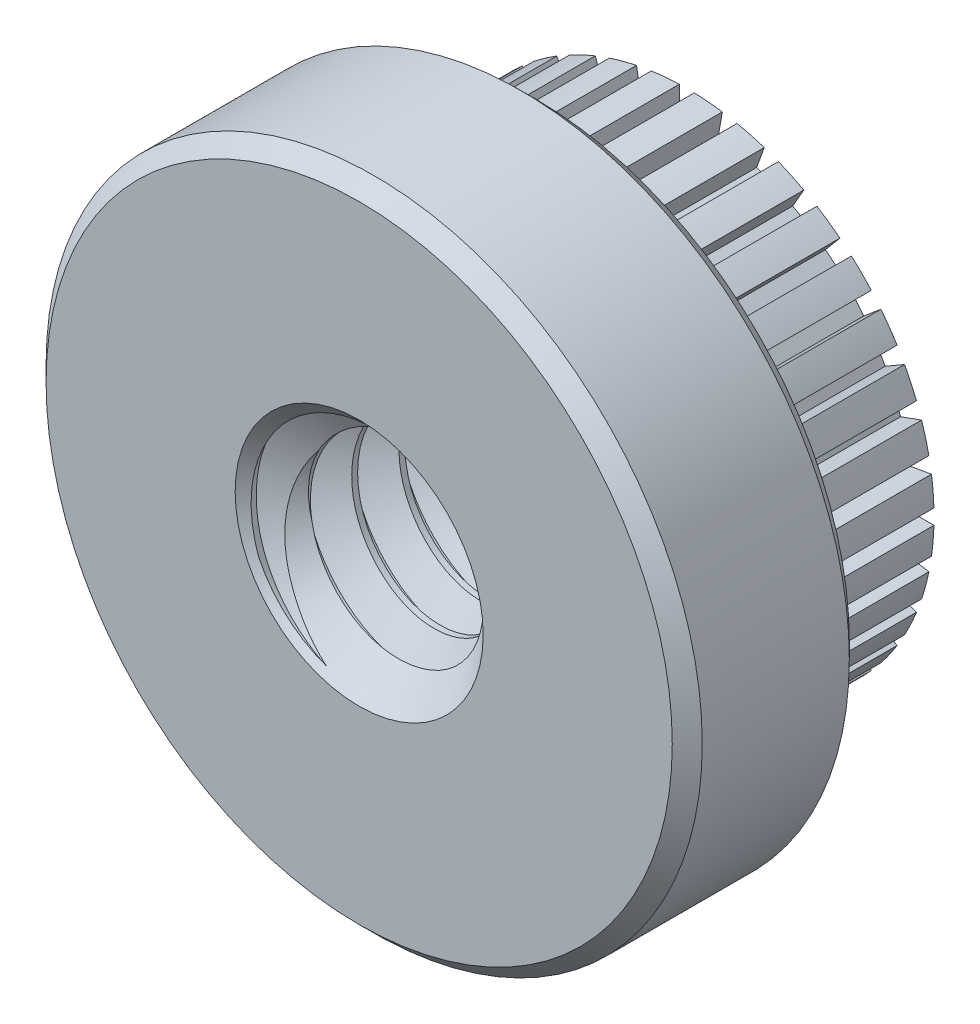
SolidWorks part; units mm, degrees
ref_plane "Front Plane" through (0, 0, 0) normal (0, 0, 1) x (1, 0, 0)
ref_plane "Top Plane" through (0, 0, 0) normal (0, 1, 0) x (1, 0, 0)
ref_plane "Right Plane" through (0, 0, 0) normal (1, 0, 0) x (0, 0, -1)
sketch "Sketch1" plane through (0, 0, 0) normal (0, 0, 1) x (1, 0, 0)
  circle A0 centre (0, 0) radius 2.78
  dimension "A" = 5.56
extrude "Extrude1" add sketch "Sketch1" against normal blind 1.5
sketch "Sketch2" plane through (0, 0, -1.5) normal (0, 0, -1) x (-1, 0, 0)
  circle A0 centre (0, 0) radius 2.095
  dimension "C" = 4.19
extrude "Extrude2" add sketch "Sketch2" along normal blind 1.53
sketch "Sketch3" plane through (0, 0, -3.03) normal (0, 0, -1) x (-1, 0, 0)
  line L0 (0, 1.9045) -> (0, 2.78)
  circle A1 centre (0, 0) radius 2.78 construction
  circle A2 centre (0, 0) radius 1.9045
  circle A3 centre (0, 0) radius 1.9045 construction
  dimension "D1" = 0.1905
extrude "Cut-Extrude-Thin1" cut sketch "Sketch3" against normal up to surface (1.53 mm away) thin up to face at (2.78, 0, -1.5) thin type mid plane wall 0.127
pattern_circular "CirPattern1" count 36 over 360 about axis through (0, 0, -1.5) along (0, 0, 1) of "Cut-Extrude-Thin1"
sketch "Sketch5" plane through (0, 0, -3.03) normal (0, 0, -1) x (-1, 0, 0)
  circle A2 centre (0, 0) radius 1.6505
  circle A3 centre (0, 0) radius 1.6505
  dimension "D1" = 0.254
extrude "Cut-Extrude1" cut sketch "Sketch5" against normal blind 0.254 flip side to cut
chamfer "Chamfer1" distance 0.127 angle 45 1 edges at (-1.6505, 0, -3.03)
sketch "Sketch6" plane through (0, 0, -1.5) normal (0, 0, -1) x (-1, 0, 0)
  circle A0 centre (0, 0) radius 1.6505 construction
  circle A1 centre (0, 0) radius 1.6505
  circle A2 centre (0, 0) radius 2.78 construction
  circle A3 centre (0, 0) radius 2.78
extrude "Cut-Extrude2" cut sketch "Sketch6" along normal blind 0.127
chamfer "Chamfer2" distance 0.127 angle 45 2 edges at (2.78, 0, 0) (2.78, 0, -1.5)
sketch "Sketch7" plane through (0, 0, 0) normal (0, 0, 1) x (1, 0, 0)
  circle A0 centre (0, 0) radius 1
  dimension "Thread Od" = 2
extrude "Cut-Extrude3" cut sketch "Sketch7" against normal through all
sketch "Sketch8" plane through (0, 0, -3.03) normal (0, 0, -1) x (-1, 0, 0)
  circle A0 centre (0, 0) radius 1 construction
  circle A1 centre (0, 0) radius 1
curve "Helix/Spiral1" pitch 0.4 height 4.5 radius 1 centre (0, 0, -3.03) axis (0, 0, 1) start towards (0, 1, 0) parameters "pitch"=0.4
sketch "Sketch9" plane through (0, 0, 0) normal (1, 0, 0) x (0, 0, -1)
  line L0 (3.38, 1) -> (3.23, 0.7402)
  line L1 (3.23, 0.7402) -> (3.18, 0.7402)
  line L2 (3.18, 0.7402) -> (3.03, 1)
  line L3 (3.38, 1) -> (3.03, 1)
  line L4 (3.205, 1) -> (3.205, 0.7402) construction
  line L5 (3.305, 0.8701) -> (3.105, 0.8701) construction
  line L6 (3.03, -1) -> (3.03, 1) construction
  dimension "D1" = 60
  dimension "D2" = 0.05
sweep "Sweep1" add profiles "Sketch9" path "Helix/Spiral1"
sketch "Sketch10" plane through (0, 0, 0) normal (0, 0, 1) x (1, 0, 0)
  circle A1 centre (0, 0) radius 2.653
  circle A2 centre (0, 0) radius 2.653
  dimension "D1" = 0
extrude "Cut-Extrude4" cut sketch "Sketch10" along normal through all
sketch "Sketch11" plane through (0, 0, -3.03) normal (0, 0, -1) x (-1, 0, 0)
  circle A0 centre (0, 0) radius 1.5235 construction
  circle A1 centre (0, 0) radius 1.5235
extrude "Cut-Extrude5" cut sketch "Sketch11" along normal through all
sketch "Sketch13" plane through (0, 0, 0) normal (0, 0, 1) x (1, 0, 0)
  circle A2 centre (0, 0) radius 1.0508
  circle A3 centre (0, 0) radius 1.0508
  dimension "D1" = 0.0508
extrude "Cut-Extrude6" cut sketch "Sketch13" against normal through all draft 45
sketch "Sketch14" plane through (0, 0, -3.03) normal (0, 0, -1) x (-1, 0, 0)
  circle A2 centre (0, 0) radius 1.0508
  circle A3 centre (0, 0) radius 1.0508
  dimension "D1" = 0.0508
extrude "Cut-Extrude7" cut sketch "Sketch14" against normal through all draft 45
equation "\"D3@Helix/Spiral1\" = \"B@Extrude1\"+3"
equation "\"D2@Sketch9\" = \"pitch@Helix/Spiral1\"*.125"
equation "\"D3@Sketch9\" = \"pitch@Helix/Spiral1\"*.50"
